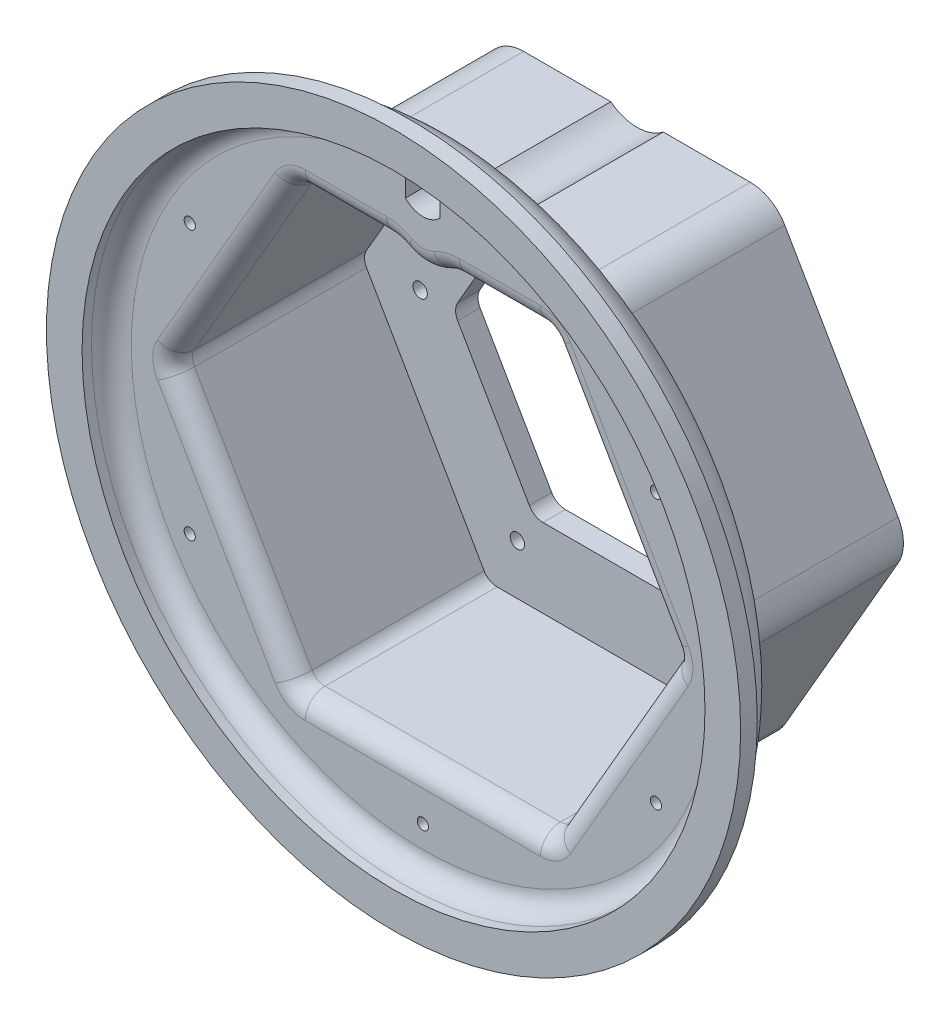
SolidWorks part; units mm, degrees
other "Markup1"
sketch "Sketch14" plane through (139.7, -139.7, 89) normal (0.2541, -0.4164, 0.8729) x (-0.8583, 0.319, 0.402)
other "Markup2"
sketch "Sketch15"
other "Markup3"
sketch "Sketch16"
ref_plane "Front Plane" through (0, 0, 0) normal (0, 0, 1) x (1, 0, 0)
ref_plane "Top Plane" through (0, 0, 0) normal (0, 1, 0) x (1, 0, 0)
ref_plane "Right Plane" through (0, 0, 0) normal (1, 0, 0) x (0, 0, -1)
sketch "Sketch1" plane through (0, 0, 0) normal (0, 0, 1) x (1, 0, 0)
  line L0 (0, 0) -> (101.6136, 0) construction
  line L1 (101.6136, 0) -> (50.8068, 88)
  line L3 (-50.8068, 88) -> (-101.6136, 0)
  line L4 (-101.6136, 0) -> (-50.8068, -88)
  line L5 (-50.8068, -88) -> (50.8068, -88)
  line L6 (50.8068, -88) -> (101.6136, 0)
  line L7 (109.6966, 0) -> (54.8483, 95)
  line L9 (-54.8483, 95) -> (-109.6966, 0)
  line L10 (-109.6966, 0) -> (-54.8483, -95)
  line L11 (-54.8483, -95) -> (54.8483, -95)
  line L12 (54.8483, -95) -> (109.6966, 0)
  line L13 (101.6136, 0) -> (109.6966, 0) construction
  line L14 (-50.8068, 88) -> (-10.5605, 88)
  line L15 (69.6204, 95) -> (10.7307, 95) [skipped]
  line L16 (50.8068, 88) -> (10.5605, 88)
  line L17 (0, 0) -> (0, 84.322) construction
  line L18 (-54.8483, 95) -> (-10.5605, 95)
  line L19 (54.8483, 95) -> (10.5605, 95)
  line L20 (0, 84.322) -> (0, 91.322) construction
  line L21 (65.493, 88) -> (25.493, 88) [skipped]
  circle A0 centre (0, 0) radius 88 construction
  circle A1 centre (0, 0) radius 95 construction
  arc A2 (10.5605, 88) -> (-10.5605, 88) centre (0, 101.322) cw
  arc A3 (-10.5605, 95) -> (10.5605, 95) centre (0, 108.322) ccw
  dimension "D5" = 17
  dimension "D6" = 17
  dimension "D7" = 7
  dimension "D1" = 176
  dimension "D2" = 176
  dimension "D3" = 190
  dimension "D4" = 40.2463
  dimension "D8" = 190
extrude "Boss-Extrude1" add sketch "Sketch1" along normal blind 65
sketch "Sketch2" plane through (0, 0, 0) normal (0, 0, -1) x (-1, 0, 0)
  line L0 (0, 0) -> (65, 0) construction
  line L1 (65, 0) -> (32.5, 56.2917)
  line L2 (32.5, 56.2917) -> (-32.5, 56.2917)
  line L3 (-32.5, 56.2917) -> (-65, 0)
  line L4 (-65, 0) -> (-32.5, -56.2917)
  line L5 (-32.5, -56.2917) -> (32.5, -56.2917)
  line L6 (32.5, -56.2917) -> (65, 0)
  line L7 (109.6966, 0) -> (54.8483, 95)
  line L9 (-54.8483, 95) -> (-109.6966, 0)
  line L10 (-109.6966, 0) -> (-54.8483, -95)
  line L11 (-54.8483, -95) -> (54.8483, -95)
  line L12 (54.8483, -95) -> (109.6966, 0)
  line L14 (10.5605, 95) -> (54.8483, 95) construction
  line L15 (69.6204, 95) -> (10.7307, 95) [skipped]
  line L16 (-54.8483, 95) -> (-10.5605, 95) construction
  line L17 (10.5605, 95) -> (54.8483, 95)
  line L18 (-54.8483, 95) -> (-10.5605, 95)
  circle A0 centre (0, 0) radius 56.2917 construction
  circle A1 centre (0, 0) radius 95 construction
  arc A2 (-10.5605, 95) -> (10.5605, 95) centre (0, 108.322) ccw construction
  arc A3 (-10.5605, 95) -> (10.5605, 95) centre (0, 108.322) ccw
  dimension "D1" = 65
extrude "Boss-Extrude2" add sketch "Sketch2" along normal blind 9
sketch "Sketch6" plane through (0, 0, 65) normal (0, 0, 1) x (1, 0, 0)
  line L6 (101.6136, 0) -> (50.8068, 88)
  line L7 (50.8068, -88) -> (101.6136, 0)
  line L8 (-50.8068, -88) -> (50.8068, -88)
  line L9 (-101.6136, 0) -> (-50.8068, -88)
  line L10 (-50.8068, 88) -> (-101.6136, 0)
  line L11 (-10.5605, 88) -> (-50.8068, 88)
  line L12 (101.6136, 0) -> (50.8068, 88)
  line L13 (50.8068, -88) -> (101.6136, 0)
  line L14 (-50.8068, -88) -> (50.8068, -88)
  line L15 (-101.6136, 0) -> (-50.8068, -88)
  line L16 (-50.8068, 88) -> (-101.6136, 0)
  line L19 (-10.5605, 88) -> (-50.8068, 88)
  line L20 (50.8068, 88) -> (10.5605, 88)
  line L21 (50.8068, 88) -> (10.5605, 88)
  circle A0 centre (0, 0) radius 132.3
  arc A2 (-10.5605, 88) -> (10.5605, 88) centre (0, 101.322) ccw
  arc A3 (-10.5605, 88) -> (10.5605, 88) centre (0, 101.322) ccw
  dimension "D2" = 264.6
  dimension "D1" = 0
extrude "Boss-Extrude3" add sketch "Sketch6" along normal blind 12.2
sketch "Sketch3" plane through (0, 0, 0) normal (0, 0, 1) x (1, 0, 0)
  line L0 (0, 0) -> (78.3, 0)
  circle A0 centre (78.3, 0) radius 2.9
  dimension "D2" = 5.8
  dimension "D1" = 78.3
extrude "Cut-Extrude1" cut sketch "Sketch3" against normal up to next contours A0
fillet "Fillet1" radius 6.35 6 edges at (32.5, -56.2917, -4.5) (-32.5, -56.2917, -4.5) (65, 0, -4.5) (32.5, 56.2917, -4.5) (-32.5, 56.2917, -4.5) (-65, 0, -4.5)
fillet "Fillet2" radius 6 6 edges at (-50.8068, -88, 38.6) (50.8068, -88, 38.6) (101.6136, 0, 38.6) (50.8068, 88, 38.6) (-50.8068, 88, 38.6) (-101.6136, 0, 38.6)
fillet "Fillet3" radius 14 2 edges at (10.5605, 88, 38.6) (-10.5605, 88, 38.6)
fillet "Fillet6" radius 14 1 edges at (132.3, 0, 65)
sketch "Sketch12" plane through (0, 0, 77.2) normal (0, 0, 1) x (1, 0, 0)
  circle A0 centre (0, 0) radius 131.8549
  circle A1 centre (0, 0) radius 125.3549
  dimension "D1" = 6.5
extrude "Boss-Extrude5" add sketch "Sketch12" along normal blind 5.1
sketch "Sketch13" plane through (0, 0, 82.3) normal (0, 0, 1) x (1, 0, 0)
  circle A1 centre (0, 0) radius 139.7
  circle A2 centre (0, 0) radius 125.3549 construction
  circle A3 centre (0, 0) radius 125.3549
  dimension "D1" = 279.4
extrude "Boss-Extrude7" add sketch "Sketch13" along normal blind 6.7
fillet "Fillet7" radius 8 1 edges at (125.3549, 0, 77.2)
fillet "Fillet8" radius 4 1 edges at (131.8549, 0, 82.3)
fillet "Fillet9" radius 8 16 edges at (-11.2363, 87.5784, 77.2) (0, 84.322, 77.2) (11.2363, 87.5784, 77.2) (30.9944, 88, 77.2) (50.3427, 87.1962, 77.2) (76.2102, 44, 77.2) (100.6854, 0, 77.2) (76.2102, -44, 77.2) (50.3427, -87.1962, 77.2) (0, -88, 77.2) (-50.3427, -87.1962, 77.2) (-76.2102, -44, 77.2) (-100.6854, 0, 77.2) (-76.2102, 44, 77.2) (-50.3427, 87.1962, 77.2) (-30.9944, 88, 77.2)
sketch "Sketch9" plane through (0, 0, 65) normal (0, 0, -1) x (-1, 0, 0)
  line L0 (0, 0) -> (0, 91.322) construction
  line L1 (0, 91.322) -> (0, 103.322) construction
  line L2 (0, 103.322) -> (0, 106.322) construction
  line L3 (0, 106.322) -> (7, 106.322) construction
  line L4 (7, 106.322) -> (7, 119.322)
  line L5 (7, 106.322) -> (-7, 106.322) construction
  line L6 (-7, 106.322) -> (-7, 119.322)
  line L7 (-7, 119.322) -> (7, 119.322) construction
  line L8 (0, 119.322) -> (0, 122.322) construction
  arc A0 (-10.5605, 95) -> (10.5605, 95) centre (0, 108.322) ccw construction
  arc A1 (7, 106.322) -> (-7, 106.322) centre (0, 112.9887) cw
  arc A2 (-7, 119.322) -> (7, 119.322) centre (0, 112.6553) cw
  dimension "D1" = 12
  dimension "D2" = 3
  dimension "D3" = 7
  dimension "D4" = 13
  dimension "D5" = 3
extrude "Cut-Extrude2" cut sketch "Sketch9" against normal through all
pattern_circular "CirPattern1" count 6 over 360 about axis through (0, 0, 89) along (0, 0, -1) of "Cut-Extrude1" reverse direction yes
fillet "Fillet11" radius 16 6 edges at (-109.6966, 0, 28) (-54.8483, 95, 28) (54.8483, 95, 28) (109.6966, 0, 28) (54.8483, -95, 28) (-54.8483, -95, 28)
fillet "Fillet10" radius 4 14 edges at (-82.2724, -47.5, 65) (0, -95, 65) (82.2724, -47.5, 65) (82.2724, 47.5, 65) (28.0856, 95, 65) (0, 91.322, 65) (-28.0856, 95, 65) (-82.2724, 47.5, 65) (-53.6107, 92.8564, 65) (53.6107, 92.8564, 65) (107.2213, 0, 65) (53.6107, -92.8564, 65) (-53.6107, -92.8564, 65) (-107.2213, 0, 65)
sketch "Sketch17" plane through (0, 0, 77.2) normal (0, 0, 1) x (1, 0, 0)
  line L0 (0, 0) -> (83.1384, 48) construction
  line L1 (59.4671, 89) -> (106.8098, 7) construction
  line L2 (83.1384, 48) -> (104.486, 60.325) construction
  circle A0 centre (0, 0) radius 120.65
  circle A1 centre (93.8122, 54.1625) radius 2
  dimension "D1" = 241.3
  dimension "D2" = 4
hole_wizard "M4 Clearance Hole1" positions "Sketch18" profile "Sketch19" hole size "M4" standard "ANSI Metric" end condition up to next
sketch "Sketch18" plane through (0, 0, 77.2) normal (0, 0, 1) x (1, 0, 0)
  point P0 (93.8122, 54.1625)
sketch "Sketch19" plane through (93.8122, 54.1625, 77.2) normal (1, 0, 0) x (0, -1, 0)
  line L0 (0, 0) -> (0, 12.2)
  line L1 (0, 12.2) -> (2.25, 12.2)
  line L2 (2.25, 12.2) -> (2.25, 0)
  line L5 (2.25, 0) -> (0, 0)
  line L11 (0, -6.35) -> (0, 107.95) construction
  dimension "Thru Hole Dia." = 4.5
  dimension "Thru Hole Depth" = 12.2
pattern_circular "CirPattern2" count 6 over 360 about axis through (0, 0, 89) along (0, 0, -1) skipping 5 of "M4 Clearance Hole1"
